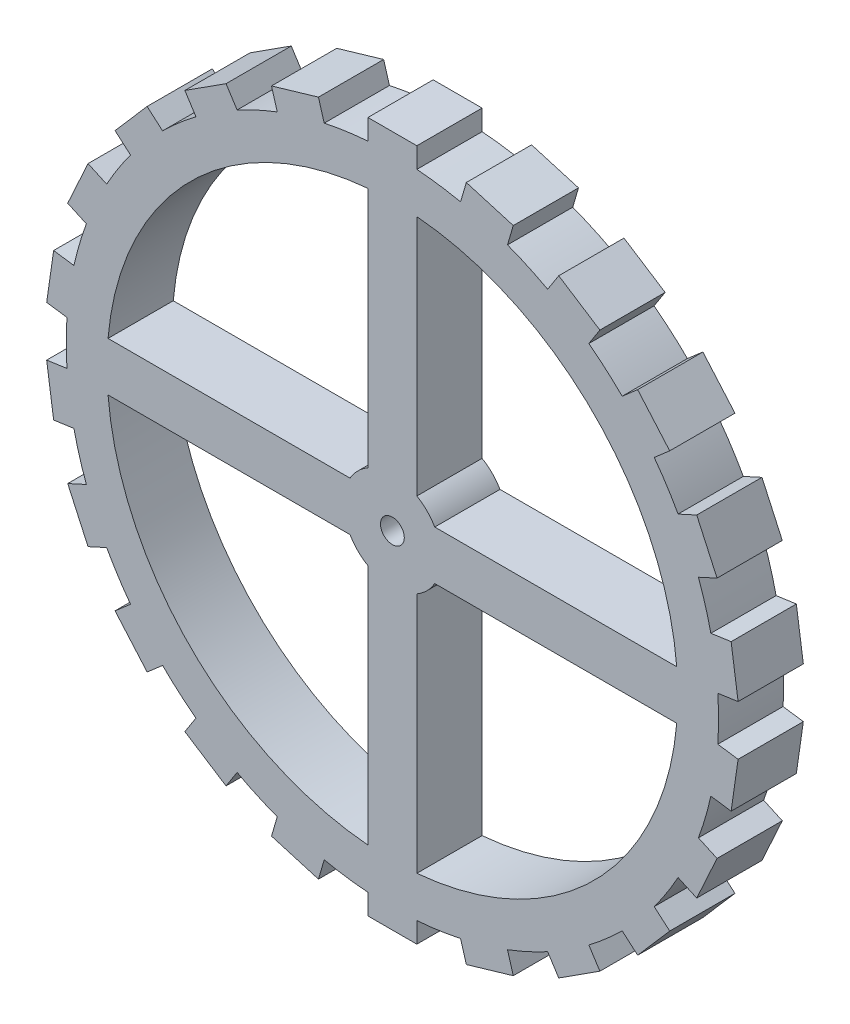
SolidWorks part; units mm, degrees
ref_plane "Front Plane" through (0, 0, 0) normal (0, 0, 1) x (1, 0, 0)
ref_plane "Top Plane" through (0, 0, 0) normal (0, 1, 0) x (1, 0, 0)
ref_plane "Right Plane" through (0, 0, 0) normal (1, 0, 0) x (0, 0, -1)
sketch "Sketch1" plane through (0, 0, 0) normal (0, 0, 1) x (1, 0, 0)
  line L0 (-1.905, 3.2996) -> (-1.905, 22.1432)
  line L2 (1.905, -22.1432) -> (1.905, -3.2996)
  line L4 (-1.905, -22.1432) -> (-1.905, -3.2996)
  line L5 (1.905, -22.1432) -> (-1.905, 22.1432) construction
  line L6 (1.905, 22.1432) -> (-1.905, -22.1432) construction
  line L7 (-22.1432, -1.905) -> (-3.2996, -1.905)
  line L9 (-22.1432, 1.905) -> (-3.2996, 1.905)
  line L11 (-22.1432, -1.905) -> (22.1432, 1.905) construction
  line L12 (-22.1432, 1.905) -> (22.1432, -1.905) construction
  line L13 (3.2996, 1.905) -> (22.1432, 1.905)
  line L14 (3.2996, -1.905) -> (22.1432, -1.905)
  line L15 (1.905, 3.2996) -> (1.905, 22.1432)
  circle A0 centre (0, 0) radius 25.4
  arc A1 (-22.1432, -1.905) -> (-1.905, -22.1432) centre (0, 0) ccw
  circle A2 centre (0, 0) radius 0.9271
  arc A4 (-3.2996, -1.905) -> (-1.905, -3.2996) centre (0, 0) ccw
  arc A5 (-1.905, 3.2996) -> (-3.2996, 1.905) centre (0, 0) ccw
  arc A6 (3.2996, 1.905) -> (1.905, 3.2996) centre (0, 0) ccw
  arc A7 (1.905, -3.2996) -> (3.2996, -1.905) centre (0, 0) ccw
  arc A8 (1.905, -22.1432) -> (22.1432, -1.905) centre (0, 0) ccw
  arc A9 (22.1432, 1.905) -> (1.905, 22.1432) centre (0, 0) ccw
  arc A10 (-1.905, 22.1432) -> (-22.1432, 1.905) centre (0, 0) ccw
  dimension "D1" = 50.8
  dimension "D2" = 44.45
  dimension "D3" = 1.8542
  dimension "D5" = 3.81
  dimension "D6" = 3.81
extrude "Boss-Extrude1" add sketch "Sketch1" along normal blind 5.08
sketch "Sketch2" plane through (0, 0, 5.08) normal (0, 0, 1) x (1, 0, 0)
  line L0 (5.308, 24.8392) -> (5.7575, 26.3701)
  line L2 (-1.905, 25.3285) -> (-1.905, 26.924)
  line L3 (-1.905, 26.924) -> (1.905, 26.924)
  line L4 (1.905, 25.3285) -> (1.905, 26.924)
  line L5 (0, 25.4) -> (1.905, 26.924) construction
  line L6 (-1.905, 26.924) -> (1.905, 23.876) construction
  line L7 (5.7575, 26.3701) -> (9.4132, 25.2967)
  line L8 (8.9637, 23.7658) -> (9.4132, 25.2967)
  line L9 (7.156, 24.3711) -> (9.4132, 25.2967) construction
  line L10 (5.7575, 26.3701) -> (8.5545, 22.3722) construction
  line L11 (12.091, 22.3376) -> (12.9536, 23.6798)
  line L12 (12.9536, 23.6798) -> (16.1588, 21.62)
  line L13 (15.2962, 20.2777) -> (16.1588, 21.62)
  line L14 (13.7323, 21.3678) -> (16.1588, 21.62) construction
  line L15 (12.9536, 23.6798) -> (14.5109, 19.0558) construction
  line L16 (17.8945, 18.0263) -> (19.1003, 19.0712)
  line L17 (19.1003, 19.0712) -> (21.5953, 16.1918)
  line L18 (20.3895, 15.1469) -> (21.5953, 16.1918)
  line L19 (19.196, 16.6335) -> (21.5953, 16.1918) construction
  line L20 (19.1003, 19.0712) -> (19.2918, 14.1958) construction
  line L21 (22.2482, 12.2547) -> (23.6996, 12.9175)
  line L22 (23.6996, 12.9175) -> (25.2823, 9.4518)
  line L23 (23.8309, 8.789) -> (25.2823, 9.4518)
  line L24 (23.1047, 10.5515) -> (25.2823, 9.4518) construction
  line L25 (23.6996, 12.9175) -> (22.5097, 8.1856) construction
  line L26 (24.7995, 5.4902) -> (26.3788, 5.7173)
  line L27 (26.3788, 5.7173) -> (26.9211, 1.9461)
  line L28 (25.3418, 1.719) -> (26.9211, 1.9461)
  line L29 (25.1415, 3.6148) -> (26.9211, 1.9461) construction
  line L30 (26.3788, 5.7173) -> (23.9041, 1.5123) construction
  line L31 (25.3418, -1.719) -> (26.9211, -1.9461)
  line L32 (26.9211, -1.9461) -> (26.3788, -5.7173)
  line L33 (24.7995, -5.4902) -> (26.3788, -5.7173)
  line L34 (25.1415, -3.6148) -> (26.3788, -5.7173) construction
  line L35 (26.9211, -1.9461) -> (23.3619, -5.2835) construction
  line L36 (23.8309, -8.789) -> (25.2823, -9.4518)
  line L37 (25.2823, -9.4518) -> (23.6996, -12.9175)
  line L38 (22.2482, -12.2547) -> (23.6996, -12.9175)
  line L39 (23.1047, -10.5515) -> (23.6996, -12.9175) construction
  line L40 (25.2823, -9.4518) -> (20.927, -11.6513) construction
  line L41 (20.3895, -15.1469) -> (21.5953, -16.1918)
  line L42 (21.5953, -16.1918) -> (19.1003, -19.0712)
  line L43 (17.8945, -18.0263) -> (19.1003, -19.0712)
  line L44 (19.196, -16.6335) -> (19.1003, -19.0712) construction
  line L45 (21.5953, -16.1918) -> (16.7968, -17.0752) construction
  line L46 (15.2962, -20.2777) -> (16.1588, -21.62)
  line L47 (16.1588, -21.62) -> (12.9536, -23.6798)
  line L48 (12.091, -22.3376) -> (12.9536, -23.6798)
  line L49 (13.7323, -21.3678) -> (12.9536, -23.6798) construction
  line L50 (16.1588, -21.62) -> (11.3058, -21.1157) construction
  line L51 (8.9637, -23.7658) -> (9.4132, -25.2967)
  line L52 (9.4132, -25.2967) -> (5.7575, -26.3701)
  line L53 (5.308, -24.8392) -> (5.7575, -26.3701)
  line L54 (7.156, -24.3711) -> (5.7575, -26.3701) construction
  line L55 (9.4132, -25.2967) -> (4.8988, -23.4456) construction
  line L56 (1.905, -25.3285) -> (1.905, -26.924)
  line L57 (1.905, -26.924) -> (-1.905, -26.924)
  line L58 (-1.905, -25.3285) -> (-1.905, -26.924)
  line L59 (0, -25.4) -> (-1.905, -26.924) construction
  line L60 (1.905, -26.924) -> (-1.905, -23.876) construction
  line L61 (-5.308, -24.8392) -> (-5.7575, -26.3701)
  line L62 (-5.7575, -26.3701) -> (-9.4132, -25.2967)
  line L63 (-8.9637, -23.7658) -> (-9.4132, -25.2967)
  line L64 (-7.156, -24.3711) -> (-9.4132, -25.2967) construction
  line L65 (-5.7575, -26.3701) -> (-8.5545, -22.3722) construction
  line L66 (-12.091, -22.3376) -> (-12.9536, -23.6798)
  line L67 (-12.9536, -23.6798) -> (-16.1588, -21.62)
  line L68 (-15.2962, -20.2777) -> (-16.1588, -21.62)
  line L69 (-13.7323, -21.3678) -> (-16.1588, -21.62) construction
  line L70 (-12.9536, -23.6798) -> (-14.5109, -19.0558) construction
  line L71 (-17.8945, -18.0263) -> (-19.1003, -19.0712)
  line L72 (-19.1003, -19.0712) -> (-21.5953, -16.1918)
  line L73 (-20.3895, -15.1469) -> (-21.5953, -16.1918)
  line L74 (-19.196, -16.6335) -> (-21.5953, -16.1918) construction
  line L75 (-19.1003, -19.0712) -> (-19.2918, -14.1958) construction
  line L76 (-22.2482, -12.2547) -> (-23.6996, -12.9175)
  line L77 (-23.6996, -12.9175) -> (-25.2823, -9.4518)
  line L78 (-23.8309, -8.789) -> (-25.2823, -9.4518)
  line L79 (-23.1047, -10.5515) -> (-25.2823, -9.4518) construction
  line L80 (-23.6996, -12.9175) -> (-22.5097, -8.1856) construction
  line L81 (-24.7995, -5.4902) -> (-26.3788, -5.7173)
  line L82 (-26.3788, -5.7173) -> (-26.9211, -1.9461)
  line L83 (-25.3418, -1.719) -> (-26.9211, -1.9461)
  line L84 (-25.1415, -3.6148) -> (-26.9211, -1.9461) construction
  line L85 (-26.3788, -5.7173) -> (-23.9041, -1.5123) construction
  line L86 (-25.3418, 1.719) -> (-26.9211, 1.9461)
  line L87 (-26.9211, 1.9461) -> (-26.3788, 5.7173)
  line L88 (-24.7995, 5.4902) -> (-26.3788, 5.7173)
  line L89 (-25.1415, 3.6148) -> (-26.3788, 5.7173) construction
  line L90 (-26.9211, 1.9461) -> (-23.3619, 5.2835) construction
  line L91 (-23.8309, 8.789) -> (-25.2823, 9.4518)
  line L92 (-25.2823, 9.4518) -> (-23.6996, 12.9175)
  line L93 (-22.2482, 12.2547) -> (-23.6996, 12.9175)
  line L94 (-23.1047, 10.5515) -> (-23.6996, 12.9175) construction
  line L95 (-25.2823, 9.4518) -> (-20.927, 11.6513) construction
  line L96 (-20.3895, 15.1469) -> (-21.5953, 16.1918)
  line L97 (-21.5953, 16.1918) -> (-19.1003, 19.0712)
  line L98 (-17.8945, 18.0263) -> (-19.1003, 19.0712)
  line L99 (-19.196, 16.6335) -> (-19.1003, 19.0712) construction
  line L100 (-21.5953, 16.1918) -> (-16.7968, 17.0752) construction
  line L101 (-15.2962, 20.2777) -> (-16.1588, 21.62)
  line L102 (-16.1588, 21.62) -> (-12.9536, 23.6798)
  line L103 (-12.091, 22.3376) -> (-12.9536, 23.6798)
  line L104 (-13.7323, 21.3678) -> (-12.9536, 23.6798) construction
  line L105 (-16.1588, 21.62) -> (-11.3058, 21.1157) construction
  line L106 (-8.9637, 23.7658) -> (-9.4132, 25.2967)
  line L107 (-9.4132, 25.2967) -> (-5.7575, 26.3701)
  line L108 (-5.308, 24.8392) -> (-5.7575, 26.3701)
  line L109 (-7.156, 24.3711) -> (-5.7575, 26.3701) construction
  line L110 (-9.4132, 25.2967) -> (-4.8988, 23.4456) construction
  circle A0 centre (0, 0) radius 25.4 construction
  arc A1 (1.905, 25.3285) -> (-1.905, 25.3285) centre (0, 0) ccw
  arc A2 (8.9637, 23.7658) -> (5.308, 24.8392) centre (0, 0) ccw
  arc A3 (15.2962, 20.2777) -> (12.091, 22.3376) centre (0, 0) ccw
  arc A4 (20.3895, 15.1469) -> (17.8945, 18.0263) centre (0, 0) ccw
  arc A5 (23.8309, 8.789) -> (22.2482, 12.2547) centre (0, 0) ccw
  arc A6 (25.3418, 1.719) -> (24.7995, 5.4902) centre (0, 0) ccw
  arc A7 (24.7995, -5.4902) -> (25.3418, -1.719) centre (0, 0) ccw
  arc A8 (22.2482, -12.2547) -> (23.8309, -8.789) centre (0, 0) ccw
  arc A9 (17.8945, -18.0263) -> (20.3895, -15.1469) centre (0, 0) ccw
  arc A10 (12.091, -22.3376) -> (15.2962, -20.2777) centre (0, 0) ccw
  arc A11 (5.308, -24.8392) -> (8.9637, -23.7658) centre (0, 0) ccw
  arc A12 (-1.905, -25.3285) -> (1.905, -25.3285) centre (0, 0) ccw
  arc A13 (-8.9637, -23.7658) -> (-5.308, -24.8392) centre (0, 0) ccw
  arc A14 (-15.2962, -20.2777) -> (-12.091, -22.3376) centre (0, 0) ccw
  arc A15 (-20.3895, -15.1469) -> (-17.8945, -18.0263) centre (0, 0) ccw
  arc A16 (-23.8309, -8.789) -> (-22.2482, -12.2547) centre (0, 0) ccw
  arc A17 (-25.3418, -1.719) -> (-24.7995, -5.4902) centre (0, 0) ccw
  arc A18 (-24.7995, 5.4902) -> (-25.3418, 1.719) centre (0, 0) ccw
  arc A19 (-22.2482, 12.2547) -> (-23.8309, 8.789) centre (0, 0) ccw
  arc A20 (-17.8945, 18.0263) -> (-20.3895, 15.1469) centre (0, 0) ccw
  arc A21 (-12.091, 22.3376) -> (-15.2962, 20.2777) centre (0, 0) ccw
  arc A22 (-5.308, 24.8392) -> (-8.9637, 23.7658) centre (0, 0) ccw
  point P0 (0, 25.4)
  point P14 (7.156, 24.3711)
  point P21 (13.7323, 21.3678)
  point P28 (19.196, 16.6335)
  point P35 (23.1047, 10.5515)
  point P42 (25.1415, 3.6148)
  point P49 (25.1415, -3.6148)
  point P56 (23.1047, -10.5515)
  point P63 (19.196, -16.6335)
  point P70 (13.7323, -21.3678)
  point P77 (7.156, -24.3711)
  point P84 (0, -25.4)
  point P91 (-7.156, -24.3711)
  point P98 (-13.7323, -21.3678)
  point P105 (-19.196, -16.6335)
  point P112 (-23.1047, -10.5515)
  point P119 (-25.1415, -3.6148)
  point P126 (-25.1415, 3.6148)
  point P133 (-23.1047, 10.5515)
  point P140 (-19.196, 16.6335)
  point P147 (-13.7323, 21.3678)
  point P154 (-7.156, 24.3711)
  dimension "D1" = 3.048
  dimension "D2" = 3.81
  dimension "D3" = 22
extrude "Boss-Extrude2" add sketch "Sketch2" against normal up to surface (5.08 mm away) up to face at (8.259, -8.259, 0)
